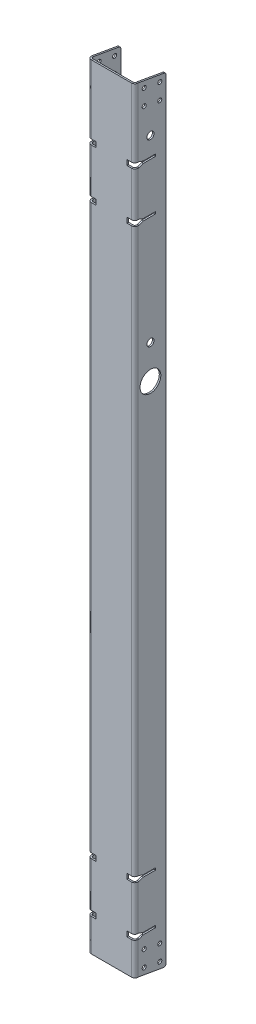
SolidWorks part; units mm, degrees
note: The reader was unsure of these and kept them because the rebuilt part matched: flange length of "Edge-Flange1", "Edge-Flange2".
ref_plane "Front Plane" through (0, 0, 0) normal (0, 0, 1) x (1, 0, 0)
ref_plane "Top Plane" through (0, 0, 0) normal (0, 1, 0) x (1, 0, 0)
ref_plane "Right Plane" through (0, 0, 0) normal (1, 0, 0) x (0, 0, -1)
sketch "Sketch1" plane through (0, 0, 0) normal (0, 0, 1) x (1, 0, 0)
  line L1 (28.575, 473.329) -> (-28.575, 473.329)
  line L2 (28.575, 473.329) -> (28.575, -473.329)
  line L3 (28.575, -473.329) -> (-28.575, -473.329)
  line L4 (-28.575, 473.329) -> (-28.575, -473.329)
  line L5 (28.575, 473.329) -> (-28.575, -473.329) construction
  line L6 (28.575, -473.329) -> (-28.575, 473.329) construction
  point P0 (0, 0)
  dimension "D1" = 57.15
  dimension "D2" = 946.658
base flange "Base-Flange1" sketch "Sketch1" thickness 1.8974 reverse thickness direction no parameters "D1"=2.032
edge flange "Edge-Flange1" sketch "Sketch8" flange angle 90 flange length 38.1 flange position material inside bend radius 2.032 thickness 1.8974 relief rectangular parameters "D6"=10
sketch "Sketch8" plane through (28.575, 0, -1.8974) normal (-1, 0, 0) x (0, 1, 0)
  line L0 (473.329, 2.8778) -> (467.4529, 36.2026)
  line L2 (-473.329, 0) -> (-473.329, 2.8778)
  line L3 (-479.2051, 36.2026) -> (467.4529, 36.2026)
  line L4 (473.329, 2.8778) -> (473.329, 0)
  line L5 (473.329, 0) -> (-473.329, 0) construction
  line L6 (473.329, 0) -> (-473.329, 0)
  line L7 (-473.329, 2.8778) -> (-479.2051, 36.2026)
  line L8 (473.329, -1.8974) -> (-473.329, -1.8974) construction
  dimension "D1" = 10
  dimension "D2" = 10
  dimension "D3" = 4.7752
  dimension "D4" = 4.7752
  dimension "D5" = 38.1
bend "EdgeBend1" bend radius 2.032 bend angle 90 parameters "D5"=1
edge flange "Edge-Flange2" sketch "Sketch11" flange angle 90 flange length 38.1 flange position material inside bend radius 2.032 thickness 1.8974 relief rectangular parameters "D6"=10
sketch "Sketch11" plane through (-28.575, 0, -1.8974) normal (1, 0, 0) x (0, -1, 0)
  line L0 (-473.329, 2.8778) -> (-467.4529, 36.2026)
  line L2 (-473.329, 0) -> (-473.329, 2.8778)
  line L3 (-467.4529, 36.2026) -> (479.2051, 36.2026)
  line L4 (473.329, 2.8778) -> (473.329, 0)
  line L5 (473.329, 0) -> (-473.329, 0) construction
  line L6 (473.329, 0) -> (-473.329, 0)
  line L7 (473.329, 2.8778) -> (479.2051, 36.2026)
  line L8 (473.329, -1.8974) -> (-473.329, -1.8974) construction
  dimension "D1" = 10
  dimension "D2" = 4.7752
  dimension "D3" = 38.1
  dimension "D4" = 10
  dimension "D5" = 4.7752
bend "EdgeBend2" bend radius 2.032 bend angle 90 parameters "D5"=2
fillet "Fillet1" radius 2.54 4 edges at (-27.6263, 467.4529, -38.1) (27.6263, 467.4529, -38.1) (-27.6263, -479.2051, -38.1) (27.6263, -479.2051, -38.1)
sketch "Sketch12" plane through (-28.575, 0, 0) normal (-1, 0, 0) x (0, 0, 1)
  line L0 (-38.1, -476.178) -> (-38.1, 465.3216) construction
  line L2 (-30.48, -450.78) -> (-11.43, -447.421) construction
  line L3 (-11.43, -447.421) -> (-11.43, -466.7649) construction
  line L4 (-11.43, -466.7649) -> (-30.48, -470.1239) construction
  line L5 (-30.48, -470.1239) -> (-30.48, -450.78) construction
  line L6 (-4.7752, -473.329) -> (-35.1189, -478.6794) construction
  circle A0 centre (-30.48, -470.1239) radius 2.4638
  circle A1 centre (-30.48, -450.78) radius 2.4638
  circle A2 centre (-11.43, -447.421) radius 2.4638
  circle A3 centre (-11.43, -466.7649) radius 2.4638
  dimension "D1" = 4.9276
  dimension "D2" = 7.62
  dimension "D3" = 19.05
  dimension "D4" = 7.62
  dimension "D5" = 19.05
extrude "Cut-Extrude1" cut sketch "Sketch12" against normal through all normal cut yes
sketch "Sketch13" plane through (-28.575, 0, 0) normal (-1, 0, 0) x (0, 0, 1)
  line L0 (-30.48, 461.059) -> (-11.43, 464.418) construction
  line L1 (-11.43, 464.418) -> (-11.43, 445.0742) construction
  line L2 (-11.43, 445.0742) -> (-30.48, 441.7151) construction
  line L3 (-30.48, 441.7151) -> (-30.48, 461.059) construction
  line L4 (-36.0011, 467.823) -> (-4.7752, 473.329) construction
  line L5 (-38.1, -476.178) -> (-38.1, 465.3216) construction
  circle A0 centre (-30.48, 461.059) radius 2.4638
  circle A1 centre (-11.43, 464.418) radius 2.4638
  circle A2 centre (-11.43, 445.0742) radius 2.4638
  circle A3 centre (-30.48, 441.7151) radius 2.4638
  dimension "D1" = 4.9276
  dimension "D2" = 7.62
  dimension "D3" = 19.05
  dimension "D4" = 7.62
  dimension "D5" = 19.05
extrude "Cut-Extrude2" cut sketch "Sketch13" against normal through all normal cut yes
sketch "Sketch14" plane through (-28.575, 0, 0) normal (-1, 0, 0) x (0, 0, 1)
  line L0 (3.175, 389.509) -> (3.175, 383.159)
  line L1 (-10.16, 387.604) -> (-25.4, 387.604)
  line L2 (-10.16, 385.064) -> (-25.4, 385.064)
  line L3 (-25.4, 387.604) -> (-25.4, 385.064)
  line L4 (3.175, 328.549) -> (3.175, 322.199)
  line L5 (-10.16, 326.644) -> (-25.4, 326.644)
  line L6 (-10.16, 324.104) -> (-25.4, 324.104)
  line L7 (-25.4, 326.644) -> (-25.4, 324.104)
  line L8 (-3.9294, -473.329) -> (-3.9294, 473.329) construction
  line L9 (0, 473.329) -> (0, -473.329) construction
  line L10 (-10.16, 387.604) -> (-5.08, 389.509)
  line L11 (-5.08, 389.509) -> (3.175, 389.509)
  line L12 (-10.16, 385.064) -> (-5.08, 383.159)
  line L13 (-5.08, 383.159) -> (3.175, 383.159)
  line L14 (0, 473.329) -> (-3.9294, 473.329) construction
  line L15 (-10.16, 326.644) -> (-5.08, 328.549)
  line L16 (-5.08, 328.549) -> (3.175, 328.549)
  line L17 (-10.16, 324.104) -> (-5.08, 322.199)
  line L18 (-5.08, 322.199) -> (3.175, 322.199)
  dimension "D1" = 2.54
  dimension "D2" = 63.5
  dimension "D3" = 28.575
  dimension "D4" = 25.4
  dimension "D5" = 85.725
  dimension "D6" = 6.35
  dimension "D7" = 5.08
  dimension "D8" = 10.16
extrude "Cut-Extrude3" cut sketch "Sketch14" against normal blind 9.525 normal cut yes
pattern_linear "LPattern1" count 2 spacing 755.65 along (0, -1, 0) of "Cut-Extrude3"
mirror "Mirror1" about plane through (0, 0, 0) normal (1, 0, 0) of "LPattern1", "Cut-Extrude3"
sketch "Sketch15" plane through (-28.575, 0, 0) normal (-1, 0, 0) x (0, 0, 1)
  line L0 (-36.0011, 467.823) -> (-4.7752, 473.329) construction
  line L1 (-38.1, -476.178) -> (-38.1, 465.3216) construction
  circle A0 centre (-19.05, 149.9615) radius 12.7
  dimension "D1" = 315.976
  dimension "D2" = 25.4
  dimension "D3" = 19.05
extrude "Cut-Extrude4" cut sketch "Sketch15" against normal through all normal cut yes
hole_wizard "11/32 (0.34375) Diameter Hole1" positions "Sketch16" profile "Sketch17" hole size "11/32" standard "ANSI Inch" end condition through all
sketch "Sketch16" plane through (-28.575, 0, 0) normal (-1, 0, 0) x (0, 0, 1)
  line L0 (-38.1, -476.178) -> (-38.1, 465.3216) construction
  line L1 (-36.0011, 467.823) -> (-4.7752, 473.329) construction
  point P0 (-19.05, 410.2012)
  point P2 (-19.05, 191.1262)
  dimension "D1" = 19.05
  dimension "D2" = 19.05
  dimension "D3" = 59.69
  dimension "D4" = 219.075
sketch "Sketch17" plane through (-28.575, 410.2012, -19.05) normal (0, 1, 0) x (0, 0, 1)
  line L0 (0, 0) -> (0, 57.15)
  line L1 (0, 57.15) -> (4.3656, 57.15)
  line L2 (4.3656, 57.15) -> (4.3656, 0)
  line L5 (4.3656, 0) -> (0, 0)
  line L11 (0, -6.35) -> (0, 107.95) construction
  dimension "Thru Hole Dia." = 8.7312
  dimension "Thru Hole Depth" = 57.15
sketch "Bend-Lines1" [suppressed] plane through (0, 0, 0) normal (0, 1, 0) x (1, 0, 0)
sketch "Bounding-Box1" [suppressed] plane through (0, 0, 0) normal (0, 1, 0) x (1, 0, 0)
sheet metal parameters "Sheet-Metal1" thickness 1.8974 parameters "D1"=2.032
flat pattern "Flat-Pattern1" [suppressed]
sketch "Bend-Lines2" plane through (0, 0, 0) normal (0, 1, 0) x (1, 0, 0)
sketch3d "Bounding-Box2" [suppressed]
  line L0 (-26.6776, 508, 0) -> (-26.6776, -508, 0) construction
  line L1 (26.6776, 508, 0) -> (26.6776, -508, 0) construction
  line L2 (-26.6776, 508, 0) -> (26.6776, 508, 0) construction
  line L3 (-26.6776, -508, 0) -> (26.6776, -508, 0) construction
sheet metal parameters "Sheet-Metal2" thickness 1.8974 parameters "D1"=2.032
flat pattern "Flat-Pattern1"
sketch "Bend-Lines2" plane through (0, 0, 0) normal (0, 0, 1) x (1, 0, 0)
  line L0 (25.0893, -508) -> (25.0893, 508) construction
  line L1 (25.0893, -508) -> (25.0893, 508) construction
sketch3d "Bounding-Box2" [suppressed]
  line L0 (61.6009, 508, 0) -> (61.6009, -508, 0) construction
  line L1 (-26.6776, 508, 0) -> (-26.6776, -508, 0) construction
  line L2 (61.6009, 508, 0) -> (-26.6776, 508, 0) construction
  line L3 (61.6009, -508, 0) -> (-26.6776, -508, 0) construction
bend of the flat pattern "Flatten-<EdgeBend1>1"
sheet metal parameters "Sheet-Metal3" thickness 1.8974 parameters "D1"=2.032
flat pattern "Flat-Pattern1"
sketch "Bend-Lines2" plane through (0, 0, 0) normal (0, 0, 1) x (1, 0, 0)
  line L0 (25.0893, -508) -> (25.0893, 508) construction
  line L1 (25.0893, -508) -> (25.0893, 508) construction
  line L2 (-25.0893, 508) -> (-25.0893, -508) construction
  line L3 (-25.0893, 508) -> (-25.0893, -508) construction
sketch3d "Bounding-Box2" [suppressed]
  line L0 (61.6008, -513.3886, 0) -> (61.6009, 508, 0) construction
  line L1 (-61.6009, -513.3886, 0) -> (-61.6008, 508, 0) construction
  line L2 (61.6008, -513.3886, 0) -> (-61.6009, -513.3886, 0) construction
  line L3 (61.6009, 508, 0) -> (-61.6008, 508, 0) construction
bend of the flat pattern "Flatten-<EdgeBend1>1"
bend of the flat pattern "Flatten-<EdgeBend2>1"
sheet metal parameters "Sheet-Metal4" thickness 1.8974 parameters "D1"=2.032
flat pattern "Flat-Pattern1"
sketch "Bend-Lines2" plane through (0, 0, 0) normal (0, 0, 1) x (1, 0, 0)
  line L0 (25.0893, -508) -> (25.0893, 508) construction
  line L1 (25.0893, -508) -> (25.0893, 508) construction
  line L2 (-25.0893, 508) -> (-25.0893, -508) construction
  line L3 (-25.0893, 508) -> (-25.0893, -508) construction
sketch3d "Bounding-Box2" [suppressed]
  line L0 (61.6008, -513.3886, 0) -> (61.6009, 508, 0) construction
  line L1 (-61.6009, -513.3886, 0) -> (-61.6008, 508, 0) construction
  line L2 (61.6008, -513.3886, 0) -> (-61.6009, -513.3886, 0) construction
  line L3 (61.6009, 508, 0) -> (-61.6008, 508, 0) construction
bend of the flat pattern "Flatten-<EdgeBend1>1"
bend of the flat pattern "Flatten-<EdgeBend2>1"
sheet metal parameters "Sheet-Metal5" thickness 1.8974 parameters "D1"=2.032
flat pattern "Flat-Pattern1"
sketch "Bend-Lines2" plane through (0, 0, 0) normal (0, 0, 1) x (1, 0, 0)
  line L0 (26.9866, -473.329) -> (26.9866, 473.329) construction
  line L1 (26.9866, -473.329) -> (26.9866, 473.329) construction
  line L2 (-26.9866, 473.329) -> (-26.9866, -473.329) construction
  line L3 (-26.9866, 473.329) -> (-26.9866, -473.329) construction
sketch3d "Bounding-Box2" [suppressed]
  line L0 (63.4982, -478.7176, 0) -> (63.4983, 473.329, 0) construction
  line L1 (-63.4983, -478.7176, 0) -> (-63.4982, 473.329, 0) construction
  line L2 (63.4982, -478.7176, 0) -> (-63.4983, -478.7176, 0) construction
  line L3 (63.4983, 473.329, 0) -> (-63.4982, 473.329, 0) construction
bend of the flat pattern "Flatten-<EdgeBend1>1"
bend of the flat pattern "Flatten-<EdgeBend2>1"
sheet metal parameters "Sheet-Metal6" thickness 1.8974 parameters "D1"=2.032
flat pattern "Flat-Pattern1"
sketch "Bend-Lines2" plane through (0, 0, 0) normal (0, 0, 1) x (1, 0, 0)
  line L0 (26.9866, -473.329) -> (26.9866, 473.329) construction
  line L1 (26.9866, -473.329) -> (26.9866, 473.329) construction
  line L2 (-26.9866, 419.989) -> (-26.9866, 361.569) construction
  line L3 (-26.9866, 419.989) -> (-26.9866, 361.569) construction
  line L4 (-26.9866, 359.029) -> (-26.9866, -473.329) construction
  line L5 (-26.9866, 473.329) -> (-26.9866, 422.529) construction
sketch3d "Bounding-Box2" [suppressed]
  line L0 (63.4982, -478.7176, 0) -> (63.4983, 473.329, 0) construction
  line L1 (-63.4983, -478.7176, 0) -> (-63.4982, 473.329, 0) construction
  line L2 (63.4982, -478.7176, 0) -> (-63.4983, -478.7176, 0) construction
  line L3 (63.4983, 473.329, 0) -> (-63.4982, 473.329, 0) construction
bend of the flat pattern "Flatten-<EdgeBend1>1"
bend of the flat pattern "Flatten-<EdgeBend2>1"
sheet metal parameters "Sheet-Metal7" thickness 1.8974 parameters "D1"=2.032
flat pattern "Flat-Pattern1"
sketch "Bend-Lines2" plane through (0, 0, 0) normal (0, 0, 1) x (1, 0, 0)
  line L0 (26.9866, -473.329) -> (26.9866, 473.329) construction
  line L1 (26.9866, -473.329) -> (26.9866, 473.329) construction
  line L2 (-26.9866, -354.711) -> (-26.9866, -413.131) construction
  line L3 (-26.9866, -354.711) -> (-26.9866, -413.131) construction
  line L4 (-26.9866, -415.671) -> (-26.9866, -473.329) construction
  line L5 (-26.9866, 473.329) -> (-26.9866, 422.529) construction
  line L6 (-26.9866, 419.989) -> (-26.9866, 361.569) construction
  line L7 (-26.9866, 359.029) -> (-26.9866, -352.171) construction
sketch3d "Bounding-Box2" [suppressed]
  line L0 (63.4982, -478.7176, 0) -> (63.4983, 473.329, 0) construction
  line L1 (-63.4983, -478.7176, 0) -> (-63.4982, 473.329, 0) construction
  line L2 (63.4982, -478.7176, 0) -> (-63.4983, -478.7176, 0) construction
  line L3 (63.4983, 473.329, 0) -> (-63.4982, 473.329, 0) construction
bend of the flat pattern "Flatten-<EdgeBend1>1"
bend of the flat pattern "Flatten-<EdgeBend2>1"
sheet metal parameters "Sheet-Metal8" thickness 1.8974 parameters "D1"=2.032
flat pattern "Flat-Pattern1"
sketch "Bend-Lines2" plane through (0, 0, 0) normal (0, 0, 1) x (1, 0, 0)
  line L0 (26.9866, 361.569) -> (26.9866, 419.989) construction
  line L1 (26.9866, 361.569) -> (26.9866, 419.989) construction
  line L2 (-26.9866, 473.329) -> (-26.9866, 422.529) construction
  line L3 (-26.9866, 473.329) -> (-26.9866, 422.529) construction
  line L4 (-26.9866, 419.989) -> (-26.9866, 361.569) construction
  line L5 (-26.9866, 359.029) -> (-26.9866, -352.171) construction
  line L6 (-26.9866, -354.711) -> (-26.9866, -413.131) construction
  line L7 (-26.9866, -415.671) -> (-26.9866, -473.329) construction
  line L8 (26.9866, 422.529) -> (26.9866, 473.329) construction
  line L9 (26.9866, -473.329) -> (26.9866, -415.671) construction
  line L10 (26.9866, -413.131) -> (26.9866, -354.711) construction
  line L11 (26.9866, -352.171) -> (26.9866, 359.029) construction
sketch3d "Bounding-Box2" [suppressed]
  line L0 (63.4982, -478.7176, 0) -> (63.4983, 473.329, 0) construction
  line L1 (-63.4983, -478.7176, 0) -> (-63.4982, 473.329, 0) construction
  line L2 (63.4982, -478.7176, 0) -> (-63.4983, -478.7176, 0) construction
  line L3 (63.4983, 473.329, 0) -> (-63.4982, 473.329, 0) construction
bend of the flat pattern "Flatten-<EdgeBend1>1"
bend of the flat pattern "Flatten-<EdgeBend2>1"
sheet metal parameters "Sheet-Metal9" thickness 1.8974 parameters "D1"=2.032
flat pattern "Flat-Pattern1"
sketch "Bend-Lines2" plane through (0, 0, 0) normal (0, 0, 1) x (1, 0, 0)
  line L0 (26.9866, 361.569) -> (26.9866, 419.989) construction
  line L1 (26.9866, 361.569) -> (26.9866, 419.989) construction
  line L2 (-26.9866, 473.329) -> (-26.9866, 422.529) construction
  line L3 (-26.9866, 473.329) -> (-26.9866, 422.529) construction
  line L4 (-26.9866, 419.989) -> (-26.9866, 361.569) construction
  line L5 (-26.9866, 359.029) -> (-26.9866, -352.171) construction
  line L6 (-26.9866, -354.711) -> (-26.9866, -413.131) construction
  line L7 (-26.9866, -415.671) -> (-26.9866, -473.329) construction
  line L8 (26.9866, 422.529) -> (26.9866, 473.329) construction
  line L9 (26.9866, -473.329) -> (26.9866, -415.671) construction
  line L10 (26.9866, -413.131) -> (26.9866, -354.711) construction
  line L11 (26.9866, -352.171) -> (26.9866, 359.029) construction
sketch3d "Bounding-Box2" [suppressed]
  line L0 (63.4982, -478.7176, 0) -> (63.4983, 473.329, 0) construction
  line L1 (-63.4983, -478.7176, 0) -> (-63.4982, 473.329, 0) construction
  line L2 (63.4982, -478.7176, 0) -> (-63.4983, -478.7176, 0) construction
  line L3 (63.4983, 473.329, 0) -> (-63.4982, 473.329, 0) construction
bend of the flat pattern "Flatten-<EdgeBend1>1"
bend of the flat pattern "Flatten-<EdgeBend2>1"
sheet metal parameters "Sheet-Metal10" thickness 1.8974 parameters "D1"=2.032
flat pattern "Flat-Pattern1"
sketch "Bend-Lines2" plane through (0, 0, 0) normal (0, 0, 1) x (1, 0, 0)
  line L0 (26.9866, -366.141) -> (26.9866, 322.199) construction
  line L1 (26.9866, -366.141) -> (26.9866, 322.199) construction
  line L2 (-26.9866, 473.329) -> (-26.9866, 389.509) construction
  line L3 (-26.9866, 473.329) -> (-26.9866, 389.509) construction
  line L4 (-26.9866, 383.159) -> (-26.9866, 328.549) construction
  line L5 (-26.9866, 322.199) -> (-26.9866, -366.141) construction
  line L6 (-26.9866, -372.491) -> (-26.9866, -427.101) construction
  line L7 (-26.9866, -433.451) -> (-26.9866, -473.329) construction
  line L8 (26.9866, 328.549) -> (26.9866, 383.159) construction
  line L9 (26.9866, 389.509) -> (26.9866, 473.329) construction
  line L10 (26.9866, -473.329) -> (26.9866, -433.451) construction
  line L11 (26.9866, -427.101) -> (26.9866, -372.491) construction
sketch3d "Bounding-Box2" [suppressed]
  line L0 (63.4982, -478.7176, 0) -> (63.4983, 473.329, 0) construction
  line L1 (-63.4983, -478.7176, 0) -> (-63.4982, 473.329, 0) construction
  line L2 (63.4982, -478.7176, 0) -> (-63.4983, -478.7176, 0) construction
  line L3 (63.4983, 473.329, 0) -> (-63.4982, 473.329, 0) construction
bend of the flat pattern "Flatten-<EdgeBend1>1"
bend of the flat pattern "Flatten-<EdgeBend2>1"
